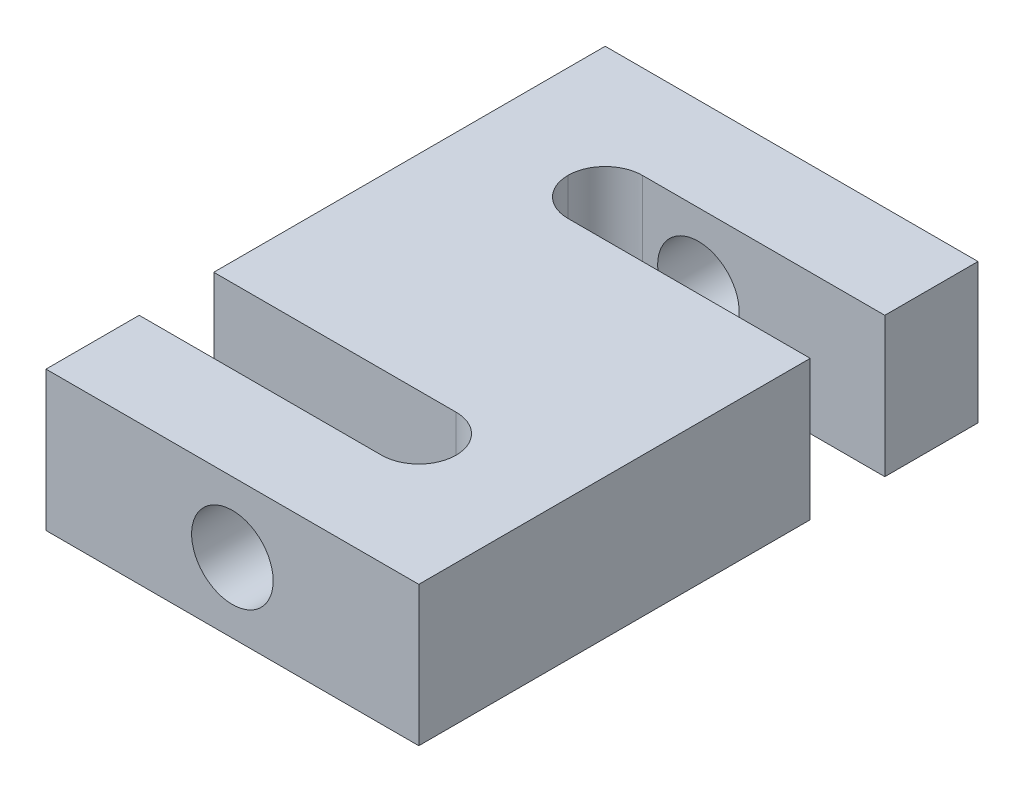
SolidWorks part; units mm, degrees
material "AISI 1020"
ref_plane "Front Plane" through (0, 0, 0) normal (0, 0, 1) x (1, 0, 0)
ref_plane "Top Plane" through (0, 0, 0) normal (0, 1, 0) x (1, 0, 0)
ref_plane "Right Plane" through (0, 0, 0) normal (1, 0, 0) x (0, 0, -1)
sketch "Sketch1" plane through (0, 0, 0) normal (0, 1, 0) x (1, 0, 0)
  line L0 (25.4, 25.4) -> (-12.7, 25.4)
  line L1 (-25.4, -38.1) -> (25.4, -38.1)
  line L2 (-25.4, -38.1) -> (-25.4, 38.1)
  line L3 (-25.4, 38.1) -> (25.4, 38.1)
  line L4 (25.4, -38.1) -> (25.4, 38.1)
  line L5 (-25.4, -38.1) -> (25.4, 38.1) construction
  line L6 (-25.4, 38.1) -> (25.4, -38.1) construction
  line L7 (-12.7, 25.4) -> (-12.7, 15.24)
  line L8 (-12.7, 15.24) -> (25.4, 15.24)
  line L9 (-25.4, -15.24) -> (12.7, -15.24)
  line L10 (12.7, -15.24) -> (12.7, -25.4)
  line L11 (12.7, -25.4) -> (-25.4, -25.4)
  point P0 (0, 0)
  dimension "D1" = 76.2
  dimension "D2" = 50.8
  dimension "D3" = 12.7
  dimension "D4" = 12.7
  dimension "D5" = 38.1
  dimension "D6" = 10.16
extrude "Boss-Extrude1" add sketch "Sketch1" along normal blind 19.05 contours L10 L11 L2 L1 L4 L8 L7 L0 L3 L9 region at (0, 0, 0)
fillet "Fillet1" radius 5.08 4 edges at (12.7, 9.525, 25.4) (12.7, 9.525, 15.24) (-12.7, 9.525, -15.24) (-12.7, 9.525, -25.4)
sketch "Sketch2" plane through (0, 0, 38.1) normal (0, 0, 1) x (1, 0, 0)
  line L1 (-25.4, 19.05) -> (25.4, 19.05) construction
  line L2 (-25.4, 19.05) -> (-25.4, 0) construction
  line L3 (-25.4, 0) -> (25.4, 0) construction
  line L4 (25.4, 19.05) -> (25.4, 0) construction
  line L5 (-25.4, 19.05) -> (25.4, 0) construction
  line L6 (-25.4, 0) -> (25.4, 19.05) construction
  circle A0 centre (0, 9.525) radius 5.5562
  point P4 (0, 9.525)
  dimension "D1" = 11.1125
extrude "Cut-Extrude1" cut sketch "Sketch2" against normal up to next
extrude "Cut-Extrude2" cut sketch "Sketch2<2>" along normal up to next from surface starting at face at (0, 9.525, -38.1)
sketch "Sketch2<2>" plane through (0, 0, 38.1) normal (0, 0, 1) x (1, 0, 0) same geometry as "Sketch2"
